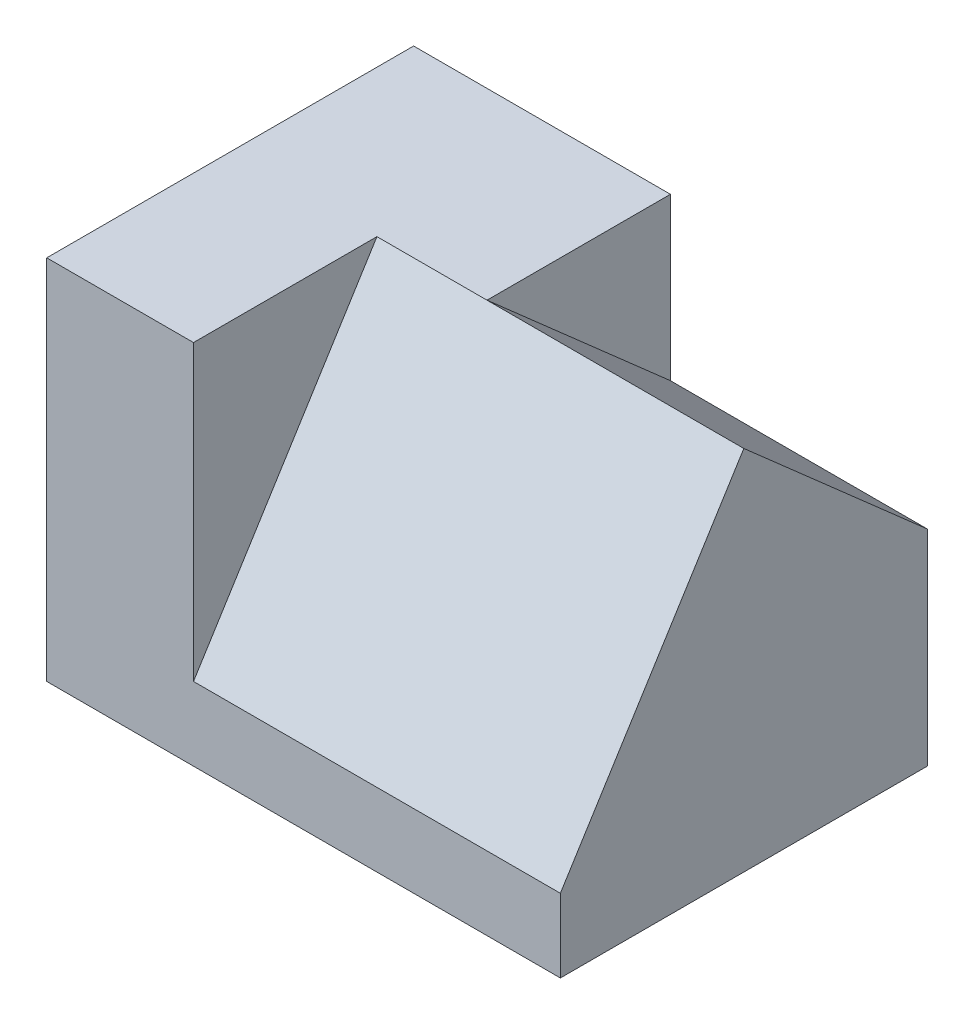
SolidWorks part; units mm, degrees
ref_plane "Front Plane" through (0, 0, 0) normal (0, 0, 1) x (1, 0, 0)
ref_plane "Top Plane" through (0, 0, 0) normal (0, 1, 0) x (1, 0, 0)
ref_plane "Right Plane" through (0, 0, 0) normal (1, 0, 0) x (0, 0, -1)
sketch "Sketch1" plane through (0, 0, 0) normal (0, 1, 0) x (1, 0, 0)
  line L1 (0, 0) -> (70, 0)
  line L2 (0, 0) -> (0, 50)
  line L3 (0, 50) -> (70, 50)
  line L4 (70, 0) -> (70, 50)
  dimension "D1" = 50
  dimension "D2" = 70
extrude "Boss-Extrude1" add sketch "Sketch1" along normal blind 10
sketch "Sketch2" plane through (0, 10, 0) normal (0, 1, 0) x (1, 0, 0)
  line L1 (70, 0) -> (20, 0)
  line L2 (70, 0) -> (70, 25)
  line L3 (70, 25) -> (20, 25)
  line L4 (20, 0) -> (20, 25)
  line L5 (70, 50) -> (35, 50)
  line L6 (70, 50) -> (70, 25)
  line L7 (70, 25) -> (35, 25)
  line L8 (35, 50) -> (35, 25)
  line M5 (0, 50) -> (0, 0)
  line M6 (0, 0) -> (70, 0)
  line M7 (70, 0) -> (70, 50)
  line M8 (70, 50) -> (0, 50)
  dimension "D1" = 50
  dimension "D2" = 25
  dimension "D4" = 35
extrude "Boss-Extrude2" add sketch "Sketch2" along normal blind 40 contours L8 L4 L3 M8 M5 M6 region at (14.7727, 10, -28.4091)
extrude "Boss-Extrude3" add sketch "Sketch2<3>" along normal blind 18 contours L8 L3 M8 M7 region at (52.5, 10, -37.5)
sketch "Sketch2<3>" plane through (0, 10, 0) normal (0, 1, 0) x (1, 0, 0) same geometry as "Sketch2"
extrude "Boss-Extrude5" add sketch "Sketch2<5>" along normal blind 40 separate body contours L4 L3 M6 M7 region at (45, 10, -12.5)
sketch "Sketch2<5>" plane through (0, 10, 0) normal (0, 1, 0) x (1, 0, 0) same geometry as "Sketch2"
ref_plane "Plane3" through (0, 2.809, 4.4944) normal (0, 0.53, 0.848) x (1, 0, 0)
sketch "Sketch10" plane through (0, 2.809, 4.4944) normal (0, 0.53, 0.848) x (1, 0, 0)
  line L1 (20, 55.6499) -> (70, 55.6499)
  line L2 (20, 55.6499) -> (20, 8.48)
  line L3 (20, 8.48) -> (70, 8.48)
  line L4 (70, 55.6499) -> (70, 8.48)
extrude "Cut-Extrude1" cut sketch "Sketch10" along normal through all
ref_plane "Plane4" through (0, 40.5771, -35.7078) normal (0, -0.7507, 0.6606) x (-1, 0, 0)
sketch "Sketch11" plane through (0, 28, 0) normal (0, 1, 0) x (1, 0, 0)
  line L3 (66.794, 50) -> (35, 50)
  point P5 (0, 0)
  point P6 (0, 0)
  point P7 (0, 0)
sketch "Sketch12" plane through (0, 28, 0) normal (0, 1, 0) x (1, 0, 0)
  line L0 (70, 25) -> (70, 50) construction
  line L1 (35, 50) -> (70, 50)
  line L2 (35, 50) -> (35, 25)
  line L3 (35, 25) -> (70, 25)
  line L4 (70, 50) -> (70, 25)
extrude "Boss-Extrude6" add sketch "Sketch12" along normal blind 22
sketch "Sketch13" plane through (0, 40.5771, -35.7078) normal (0, -0.7507, 0.6606) x (-1, 0, 0)
  line L1 (-70, -14.2636) -> (-35, -14.2636)
  line L2 (-70, -14.2636) -> (-70, 20.8661)
  line L3 (-70, 20.8661) -> (-35, 20.8661)
  line L4 (-35, -14.2636) -> (-35, 20.8661)
  point P4 (0, 0)
  point P6 (0, 0)
  dimension "D1" = 35
  dimension "D2" = 35
  dimension "D3" = 35.1297
extrude "Cut-Extrude2" cut sketch "Sketch13" against normal through all
